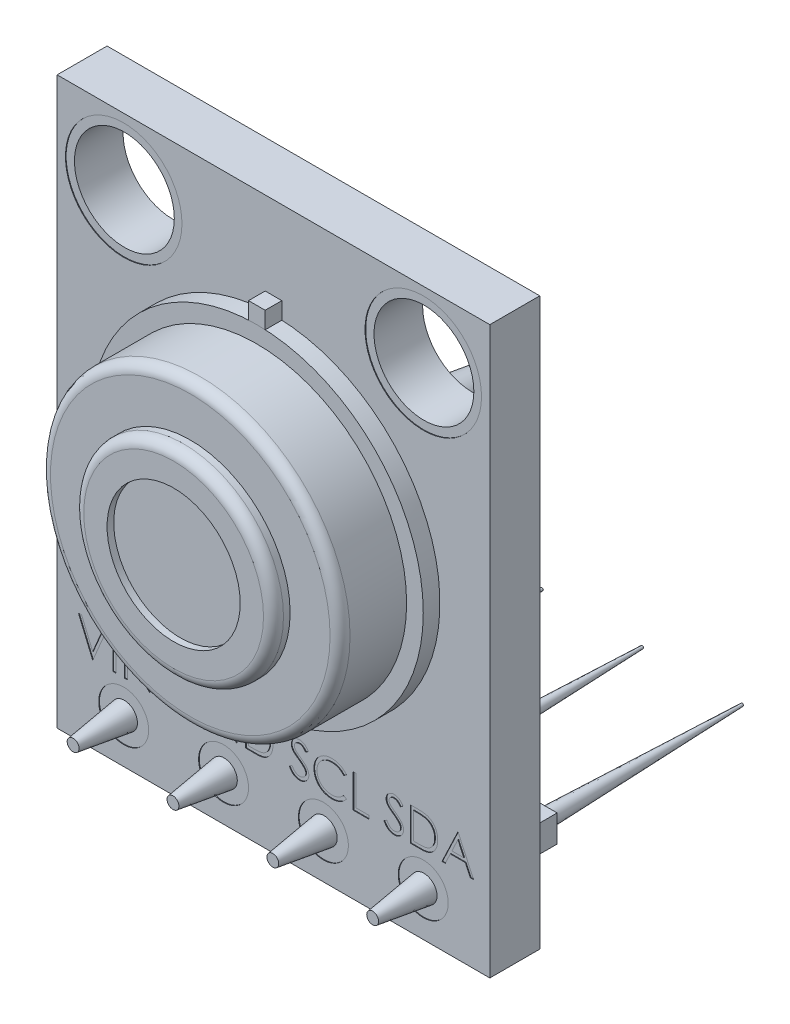
SolidWorks part; units mm, degrees
ref_plane "Ön Düzlem" through (0, 0, 0) normal (0, 0, 1) x (1, 0, 0)
ref_plane "Üst Düzlem" through (0, 0, 0) normal (0, 1, 0) x (1, 0, 0)
ref_plane "Sağ Düzlem" through (0, 0, 0) normal (1, 0, 0) x (0, 0, -1)
sketch "Çizim1" plane through (0, 0, 0) normal (0, 0, 1) x (1, 0, 0)
  line L1 (0, 0) -> (13, 0)
  line L2 (0, 0) -> (0, 17)
  line L3 (0, 17) -> (13, 17)
  line L4 (13, 0) -> (13, 17)
  dimension "D1" = 13
  dimension "D2" = 17
extrude "Yükseklik-Ekstrüzyon1" add sketch "Çizim1" along normal blind 1.5
sketch "Çizim2" plane through (0, 0, 1.5) normal (0, 0, 1) x (1, 0, 0)
  line L0 (0, 17) -> (0, 0) construction
  line L1 (13, 17) -> (0, 17) construction
  line L2 (13, 0) -> (13, 17) construction
  circle A0 centre (2, 15) radius 1.5
  circle A1 centre (11, 15) radius 1.5
  circle A2 centre (2, 1.3214) radius 0.5
  circle A3 centre (5, 1.3214) radius 0.5
  circle A4 centre (8, 1.3214) radius 0.5
  circle A5 centre (11, 1.3214) radius 0.5
  dimension "D1" = 3
  dimension "D2" = 3
  dimension "D7" = 1
  dimension "D8" = 1
  dimension "D9" = 1
  dimension "D10" = 1
  dimension "D11" = 2
  dimension "D3" = 2
  dimension "D4" = 2
  dimension "D5" = 2
  dimension "D6" = 2
  dimension "D12" = 3
  dimension "D13" = 3
  dimension "D14" = 3
  dimension "D15" = 2
extrude "Kes-Ekstrüzyon1" cut sketch "Çizim2" against normal through all
sketch "Çizim3" plane through (0, 0, 1.5) normal (0, 0, 1) x (1, 0, 0)
  circle A0 centre (2, 15) radius 1.75
  circle A1 centre (11, 15) radius 1.75
  circle A2 centre (2, 1.3214) radius 0.75
  circle A3 centre (5, 1.3214) radius 0.75
  circle A4 centre (8, 1.3214) radius 0.75
  circle A5 centre (11, 1.3214) radius 0.75
  dimension "D1" = 3.5
  dimension "D2" = 3.5
  dimension "D3" = 1.5
  dimension "D4" = 1.5
  dimension "D5" = 1.5
  dimension "D6" = 1.5
extrude "Kes-Ekstrüzyon2" cut sketch "Çizim3" against normal blind 0.02
sketch "Çizim4" plane through (0, 0, 0) normal (0, 0, -1) x (-1, 0, 0)
  circle A0 centre (-11, 15) radius 1.75 construction
  circle A1 centre (-2, 15) radius 1.75 construction
  circle A2 centre (-2, 1.3214) radius 0.75 construction
  circle A3 centre (-5, 1.3214) radius 0.75 construction
  circle A4 centre (-8, 1.3214) radius 0.75 construction
  circle A5 centre (-11, 1.3214) radius 0.75 construction
  circle A6 centre (-11, 15) radius 1.75
  circle A7 centre (-2, 15) radius 1.75
  circle A8 centre (-2, 1.3214) radius 0.75
  circle A9 centre (-5, 1.3214) radius 0.75
  circle A10 centre (-8, 1.3214) radius 0.75
  circle A11 centre (-11, 1.3214) radius 0.75
extrude "Kes-Ekstrüzyon3" cut sketch "Çizim4" against normal blind 0.02
sketch "Çizim5" plane through (0, 0, 1.5) normal (0, 0, 1) x (1, 0, 0)
  line L0 (0, 0) -> (13, 0) construction
  circle A0 centre (6.5, 9) radius 5
  point P2 (6.5, 0)
  dimension "D1" = 10
  dimension "D2" = 9
extrude "Yükseklik-Ekstrüzyon2" add sketch "Çizim5" along normal blind 0.5
sketch "Çizim6" plane through (0, 0, 2) normal (0, 0, 1) x (1, 0, 0)
  line L1 (6.25, 13.8558) -> (6.75, 13.8558)
  line L2 (6.25, 14.5) -> (6.75, 14.5)
  line L3 (6.25, 14.5) -> (6.25, 13.8558)
  line L5 (6.75, 14.5) -> (6.75, 13.8558)
  dimension "D3" = 0.5
extrude "Yükseklik-Ekstrüzyon3" add sketch "Çizim6" against normal up to surface (0.5 mm away) separate body up to face at (1.5, 9, 1.5)
sketch "Çizim7" plane through (0, 0, 2) normal (0, 0, 1) x (1, 0, 0)
  circle A0 centre (6.5, 9) radius 4.5
extrude "Yükseklik-Ekstrüzyon4" add sketch "Çizim7" along normal blind 2
sketch "Çizim8" plane through (0, 0, 4) normal (0, 0, 1) x (1, 0, 0)
  circle A0 centre (6.5, 9) radius 3
  dimension "D1" = 6
extrude "Yükseklik-Ekstrüzyon5" add sketch "Çizim8" along normal blind 0.5
fillet "Radyus1" radius 0.3 2 edges at (11, 9, 4) (9.5, 9, 4.5)
sketch "Çizim9" plane through (0, 0, 4.5) normal (0, 0, 1) x (1, 0, 0)
  circle A0 centre (6.5, 9) radius 2
  dimension "D1" = 4
extrude "Kes-Ekstrüzyon4" cut sketch "Çizim9" against normal blind 0.2
sketch "Çizim10" plane through (0, 0, 1.5) normal (0, 0, 1) x (1, 0, 0)
  text T0 " VIN GND SCL SDA" font "Century Gothic" height 1
extrude "Kes-Ekstrüzyon5" cut sketch "Çizim10" against normal blind 0.02
sketch "Çizim11" plane through (0, 0, 0) normal (0, 0, -1) x (-1, 0, 0)
  circle A0 centre (-6.805, 16.0607) radius 0.8
extrude "Yükseklik-Ekstrüzyon6" add sketch "Çizim11" along normal blind 0.02
sketch "Çizim12" plane through (0, 0, 0) normal (0, 0, -1) x (-1, 0, 0)
  line L0 (-9.25, 11.8337) -> (-9.25, 6.4736) construction
  line L1 (-3.75, 11.8337) -> (-3.75, 6.4736) construction
  line L2 (-9.25, 11.8337) -> (-3.75, 11.8337) construction
  line L3 (-9.25, 6.4736) -> (-3.75, 6.4736) construction
  circle A4 centre (-9.25, 11.8337) radius 0.75
  circle A5 centre (-3.75, 11.8337) radius 0.75
  circle A6 centre (-3.75, 6.4736) radius 0.75
  circle A7 centre (-9.25, 6.4736) radius 0.75
  dimension "D1" = 1.5
  dimension "D2" = 1.5
  dimension "D3" = 1.5
  dimension "D4" = 1.5
extrude "Yükseklik-Ekstrüzyon7" add sketch "Çizim12" along normal blind 3 draft 8
fillet "Radyus2" radius 0.3 4 edges at (3, 6.4736, 0) (8.5, 6.4736, 0) (3, 11.8337, 0) (8.5, 11.8337, 0)
sketch "Çizim13" plane through (0, 0, 0) normal (0, 0, -1) x (-1, 0, 0)
  line L0 (-11.6399, 4.8557) -> (-10.6399, 4.8557)
  line L1 (-11.6399, 5.2525) -> (-10.6399, 5.2525)
  line L2 (-11.6399, 5.2525) -> (-11.6399, 3.2525)
  line L3 (-11.6399, 3.2525) -> (-10.6399, 3.2525)
  line L4 (-10.6399, 5.2525) -> (-10.6399, 3.2525)
  line L5 (-11.6399, 5.2525) -> (-10.6399, 3.2525) construction
  line L6 (-11.6399, 3.2525) -> (-10.6399, 5.2525) construction
  line L7 (-9.0978, 5.2525) -> (-8.0978, 5.2525)
  line L8 (-9.0978, 5.2525) -> (-9.0978, 3.2525)
  line L9 (-9.0978, 3.2525) -> (-8.0978, 3.2525)
  line L10 (-8.0978, 5.2525) -> (-8.0978, 3.2525)
  line L11 (-9.0978, 5.2525) -> (-8.0978, 3.2525) construction
  line L12 (-9.0978, 3.2525) -> (-8.0978, 5.2525) construction
  line L13 (-6.919, 5.2525) -> (-5.919, 5.2525)
  line L14 (-6.919, 5.2525) -> (-6.919, 3.2525)
  line L15 (-6.919, 3.2525) -> (-5.919, 3.2525)
  line L16 (-5.919, 5.2525) -> (-5.919, 3.2525)
  line L17 (-6.919, 5.2525) -> (-5.919, 3.2525) construction
  line L18 (-6.919, 3.2525) -> (-5.919, 5.2525) construction
  line L19 (-4.3309, 5.311) -> (-2.8309, 5.311)
  line L20 (-4.3309, 5.311) -> (-4.3309, 3.111)
  line L21 (-4.3309, 3.111) -> (-2.8309, 3.111)
  line L22 (-2.8309, 5.311) -> (-2.8309, 3.111)
  line L23 (-4.3309, 5.311) -> (-2.8309, 3.111) construction
  line L24 (-4.3309, 3.111) -> (-2.8309, 5.311) construction
  line L25 (-1.561, 5.0036) -> (-0.761, 5.0036)
  line L26 (-1.561, 5.0036) -> (-1.561, 3.5036)
  line L27 (-1.561, 3.5036) -> (-0.761, 3.5036)
  line L28 (-0.761, 5.0036) -> (-0.761, 3.5036)
  line L29 (-1.561, 5.0036) -> (-0.761, 3.5036) construction
  line L30 (-1.561, 3.5036) -> (-0.761, 5.0036) construction
  line L31 (-4.3309, 4.8904) -> (-5.1309, 4.8904)
  line L32 (-4.3309, 4.8904) -> (-4.3309, 4.5904)
  line L33 (-4.3309, 4.5904) -> (-5.1309, 4.5904)
  line L34 (-5.1309, 4.8904) -> (-5.1309, 4.5904)
  line L35 (-4.3309, 3.5036) -> (-5.1309, 3.5036)
  line L36 (-4.3309, 3.5036) -> (-4.3309, 3.8036)
  line L37 (-4.3309, 3.8036) -> (-5.1309, 3.8036)
  line L38 (-5.1309, 3.5036) -> (-5.1309, 3.8036)
  line L39 (-2.8309, 4.361) -> (-2.4309, 4.361)
  line L41 (-2.8309, 4.061) -> (-2.4309, 4.061)
  line L42 (-2.4309, 4.361) -> (-2.4309, 4.061)
  line L43 (-2.8309, 4.211) -> (-2.4309, 4.061) construction
  line L44 (-2.8309, 4.211) -> (-2.4309, 4.361) construction
  line L45 (-0.761, 3.6525) -> (-1.561, 3.6525)
  line L46 (-9.0978, 4.8557) -> (-8.0978, 4.8557)
  line L47 (-10.6399, 3.6525) -> (-11.6399, 3.6525)
  line L48 (-6.919, 4.8557) -> (-5.919, 4.8557)
  line L49 (-8.0978, 3.6525) -> (-9.0978, 3.6525)
  line L51 (-5.919, 3.6525) -> (-6.919, 3.6525)
  line L54 (-1.561, 4.8557) -> (-0.761, 4.8557)
  point P0 (-11.1399, 4.2525)
  point P5 (-8.5978, 4.2525)
  point P10 (-6.419, 4.2525)
  point P15 (-3.5809, 4.211)
  point P20 (-1.161, 4.2536)
  point P33 (-2.8309, 4.211)
  dimension "D1" = 1
  dimension "D2" = 1
  dimension "D3" = 1
  dimension "D4" = 2
  dimension "D5" = 2
  dimension "D6" = 2
  dimension "D7" = 1.5
  dimension "D8" = 2.2
  dimension "D9" = 0.8
  dimension "D10" = 1.5
  dimension "D11" = 0.3969
  dimension "D12" = 0.4
  dimension "D13" = 0.3
  dimension "D14" = 0.3
  dimension "D16" = 0.8
  dimension "D17" = 0.8
  dimension "D18" = 0.3
extrude "Yükseklik-Ekstrüzyon8" add sketch "Çizim13" along normal blind 1 separate body contours L47 L4 L0 L2 | L4 L1 L2 L0 | L4 L47 L2 L3 | L10 L49 L8 L9 | L49 L10 L46 L8 | L8 L46 L10 L7 | L22 L19 L20 L21 | L54 L26 L45 L28 | L26 L54 L28 L25 | L28 L45 L26 L27 | L42 L39 L22 L41 | L38 L35 L20 L37 | L31 L34 L33 L20 | L13 L16 L15 L14
sketch "Çizim14" plane through (0, 0, -1) normal (0, 0, -1) x (-1, 0, 0)
  line L0 (-5.919, 5.2525) -> (-5.919, 3.2525) construction
  line L1 (-11.6399, 5.2525) -> (-10.6399, 5.2525)
  line L2 (-11.6399, 5.2525) -> (-11.6399, 4.8525)
  line L3 (-11.6399, 4.8525) -> (-10.6399, 4.8525)
  line L4 (-5.919, 5.2525) -> (-5.919, 4.8525)
  line L5 (-0.761, 5.0036) -> (-0.761, 3.5036) construction
  line L6 (-11.6399, 3.2525) -> (-10.6399, 3.2525)
  line L7 (-11.6399, 3.2525) -> (-11.6399, 3.6525)
  line L8 (-11.6399, 3.6525) -> (-10.6399, 3.6525)
  line L9 (-5.919, 3.2525) -> (-5.919, 3.6525)
  line L10 (-1.561, 5.0036) -> (-0.761, 5.0036)
  line L11 (-1.561, 5.0036) -> (-1.561, 4.7036)
  line L12 (-1.561, 4.7036) -> (-0.761, 4.7036)
  line L13 (-0.761, 5.0036) -> (-0.761, 4.7036)
  line L14 (-1.561, 5.0036) -> (-1.561, 3.5036) construction
  line L15 (-1.561, 3.5036) -> (-0.761, 3.5036)
  line L16 (-1.561, 3.5036) -> (-1.561, 3.8036)
  line L17 (-1.561, 3.8036) -> (-0.761, 3.8036)
  line L18 (-0.761, 3.5036) -> (-0.761, 3.8036)
  line L19 (-10.6399, 5.2525) -> (-10.6399, 4.8525)
  line L20 (-9.0978, 5.2525) -> (-9.0978, 4.8525)
  line L21 (-9.0978, 5.2525) -> (-9.0978, 3.2525) construction
  line L22 (-8.0978, 5.2525) -> (-8.0978, 4.8525)
  line L23 (-8.0978, 5.2525) -> (-8.0978, 3.2525) construction
  line L24 (-6.919, 5.2525) -> (-6.919, 4.8525)
  line L25 (-10.6399, 3.6525) -> (-10.6399, 3.2525)
  line L26 (-9.0978, 3.6525) -> (-9.0978, 3.2525)
  line L27 (-8.0978, 3.6525) -> (-8.0978, 3.2525)
  line L28 (-6.919, 3.6525) -> (-6.919, 3.2525)
  line L29 (-6.919, 5.2525) -> (-5.919, 5.2525)
  line L30 (-6.919, 4.8525) -> (-5.919, 4.8525)
  line L31 (-6.919, 3.6525) -> (-5.919, 3.6525)
  line L32 (-6.919, 3.2525) -> (-5.919, 3.2525)
  line L33 (-9.0978, 5.2525) -> (-8.0978, 5.2525)
  line L34 (-9.0978, 4.8525) -> (-8.0978, 4.8525)
  line L35 (-9.0978, 3.6525) -> (-8.0978, 3.6525)
  line L36 (-9.0978, 3.2525) -> (-8.0978, 3.2525)
  dimension "D1" = 0.4
  dimension "D2" = 0.4
  dimension "D3" = 0.3
  dimension "D4" = 0.3
extrude "Kes-Ekstrüzyon6" cut sketch "Çizim14" against normal blind 0.02
sketch "Çizim15" plane through (0, 0, -1) normal (0, 0, -1) x (-1, 0, 0)
  line L0 (-4.3309, 4.8904) -> (-4.3309, 4.5904)
  line L1 (-4.3309, 3.8036) -> (-4.3309, 3.5036)
  line L2 (-2.8309, 4.361) -> (-2.8309, 4.061)
  line L16 (-2.8309, 4.361) -> (-2.8309, 5.311)
  line L17 (-2.8309, 5.311) -> (-4.3309, 5.311)
  line L18 (-4.3309, 5.311) -> (-4.3309, 4.8904)
  line L19 (-4.3309, 4.8904) -> (-5.1309, 4.8904)
  line L20 (-5.1309, 4.8904) -> (-5.1309, 4.5904)
  line L21 (-5.1309, 4.5904) -> (-4.3309, 4.5904)
  line L22 (-4.3309, 4.5904) -> (-4.3309, 3.8036)
  line L23 (-4.3309, 3.8036) -> (-5.1309, 3.8036)
  line L24 (-5.1309, 3.8036) -> (-5.1309, 3.5036)
  line L25 (-5.1309, 3.5036) -> (-4.3309, 3.5036)
  line L26 (-4.3309, 3.5036) -> (-4.3309, 3.111)
  line L27 (-4.3309, 3.111) -> (-2.8309, 3.111)
  line L28 (-2.8309, 3.111) -> (-2.8309, 4.061)
  line L29 (-2.8309, 4.061) -> (-2.4309, 4.061)
  line L30 (-2.4309, 4.061) -> (-2.4309, 4.361)
  line L31 (-2.4309, 4.361) -> (-2.8309, 4.361)
  line L35 (-4.3309, 4.8904) -> (-5.1309, 4.8904)
  line L36 (-5.1309, 4.8904) -> (-5.1309, 4.5904)
  line L37 (-5.1309, 4.5904) -> (-4.3309, 4.5904)
  line L39 (-4.3309, 3.8036) -> (-5.1309, 3.8036)
  line L40 (-5.1309, 3.8036) -> (-5.1309, 3.5036)
  line L41 (-5.1309, 3.5036) -> (-4.3309, 3.5036)
  line L45 (-2.8309, 4.061) -> (-2.4309, 4.061)
  line L46 (-2.4309, 4.061) -> (-2.4309, 4.361)
  line L47 (-2.4309, 4.361) -> (-2.8309, 4.361)
  dimension "D1" = 0
extrude "Kes-Ekstrüzyon7" cut sketch "Çizim15" against normal blind 0.02
sketch "Çizim16" plane through (0, 0, -1) normal (0, 0, -1) x (-1, 0, 0)
  line L0 (-3.8853, 5.311) -> (-3.8853, 3.111) construction
  line L1 (-4.3309, 5.311) -> (-2.8309, 5.311) construction
  line L2 (-4.3309, 3.111) -> (-2.8309, 3.111) construction
  line L3 (-11.3066, 4.8525) -> (-11.3066, 3.6525) construction
  line L4 (-11.6399, 4.8525) -> (-10.6399, 4.8525) construction
  line L5 (-10.6399, 3.6525) -> (-11.6399, 3.6525) construction
  line L7 (-9.0978, 4.8525) -> (-8.0978, 4.8525) construction
  line L8 (-8.8772, 4.8525) -> (-8.8772, 3.6525) construction
  line L9 (-8.0978, 3.6525) -> (-9.0978, 3.6525) construction
  line L11 (-6.919, 4.8525) -> (-5.919, 4.8525) construction
  line L12 (-6.697, 4.8525) -> (-6.697, 3.6525) construction
  line L13 (-5.919, 3.6525) -> (-6.919, 3.6525) construction
  text T0 "662K" font "Century Gothic" height 0.7
  text T1 "472" font "Century Gothic" height 0.5
  text T2 "472" font "Century Gothic" height 0.5
  text T3 "472" font "Century Gothic" height 0.5
extrude "Kes-Ekstrüzyon8" cut sketch "Çizim16" against normal blind 0.02
sketch "Çizim17" plane through (0, 0, 0.02) normal (0, 0, -1) x (-1, 0, 0)
  circle A0 centre (-11, 1.3214) radius 0.5 construction
  circle A1 centre (-8, 1.3214) radius 0.5 construction
  circle A2 centre (-5, 1.3214) radius 0.5 construction
  circle A3 centre (-2, 1.3214) radius 0.5 construction
  circle A4 centre (-11, 1.3214) radius 0.5
  circle A5 centre (-8, 1.3214) radius 0.5
  circle A6 centre (-5, 1.3214) radius 0.5
  circle A7 centre (-2, 1.3214) radius 0.5
extrude "Yükseklik-Ekstrüzyon9" add sketch "Çizim17" against normal up to surface (1.46 mm away) up to face at (2.75, 1.3214, 1.48)
sketch "Çizim18" plane through (0, 0, 0.02) normal (0, 0, -1) x (-1, 0, 0)
  circle A0 centre (-11, 1.3214) radius 0.6
  circle A1 centre (-8, 1.3214) radius 0.6
  circle A2 centre (-5, 1.3214) radius 0.6
  circle A3 centre (-2, 1.3214) radius 0.6
  dimension "D1" = 1.2
  dimension "D2" = 1.2
  dimension "D3" = 1.2
  dimension "D4" = 1.2
extrude "Yükseklik-Ekstrüzyon10" add sketch "Çizim18" along normal blind 0.1 and the other way blind 3 draft 8 separate body
sketch "Çizim20" plane through (0, 0, -0.08) normal (0, 0, -1) x (-1, 0, 0)
  line L1 (-7.5575, 0.9162) -> (-8.4425, 0.9162)
  line L2 (-7.5575, 0.9162) -> (-7.5575, 1.7267)
  line L3 (-7.5575, 1.7267) -> (-8.4425, 1.7267)
  line L4 (-8.4425, 0.9162) -> (-8.4425, 1.7267)
  line L5 (-7.5575, 0.9162) -> (-8.4425, 1.7267) construction
  line L6 (-7.5575, 1.7267) -> (-8.4425, 0.9162) construction
  line L7 (-11.4425, 0.9162) -> (-10.5575, 0.9162)
  line L8 (-11.4425, 0.9162) -> (-11.4425, 1.7267)
  line L9 (-11.4425, 1.7267) -> (-10.5575, 1.7267)
  line L10 (-10.5575, 0.9162) -> (-10.5575, 1.7267)
  line L11 (-11.4425, 0.9162) -> (-10.5575, 1.7267) construction
  line L12 (-11.4425, 1.7267) -> (-10.5575, 0.9162) construction
  line L13 (-4.5575, 0.9162) -> (-5.4425, 0.9162)
  line L14 (-4.5575, 0.9162) -> (-4.5575, 1.7267)
  line L15 (-4.5575, 1.7267) -> (-5.4425, 1.7267)
  line L16 (-5.4425, 0.9162) -> (-5.4425, 1.7267)
  line L17 (-4.5575, 0.9162) -> (-5.4425, 1.7267) construction
  line L18 (-4.5575, 1.7267) -> (-5.4425, 0.9162) construction
  line L19 (-1.5575, 0.9162) -> (-2.4425, 0.9162)
  line L20 (-1.5575, 0.9162) -> (-1.5575, 1.7267)
  line L21 (-1.5575, 1.7267) -> (-2.4425, 1.7267)
  line L22 (-2.4425, 0.9162) -> (-2.4425, 1.7267)
  line L23 (-1.5575, 0.9162) -> (-2.4425, 1.7267) construction
  line L24 (-1.5575, 1.7267) -> (-2.4425, 0.9162) construction
  circle A0 centre (-8, 1.3214) radius 0.6 construction
  circle A1 centre (-11, 1.3214) radius 0.6 construction
  circle A2 centre (-5, 1.3214) radius 0.6 construction
  circle A3 centre (-2, 1.3214) radius 0.6 construction
  point P0 (-8, 1.3214)
  point P8 (-11, 1.3214)
  point P16 (-5, 1.3214)
  point P24 (-2, 1.3214)
extrude "Yükseklik-Ekstrüzyon11" add sketch "Çizim20" along normal blind 2 separate body
sketch "Çizim21" plane through (0, 0, -2.08) normal (0, 0, -1) x (-1, 0, 0)
  circle A0 centre (-11, 1.3214) radius 0.25
  circle A1 centre (-8, 1.3214) radius 0.25
  circle A2 centre (-4.9848, 1.3214) radius 0.25
  circle A3 centre (-2, 1.3214) radius 0.25
  dimension "D1" = 0.5
extrude "Yükseklik-Ekstrüzyon12" add sketch "Çizim21" along normal blind 6 draft 2 separate body
